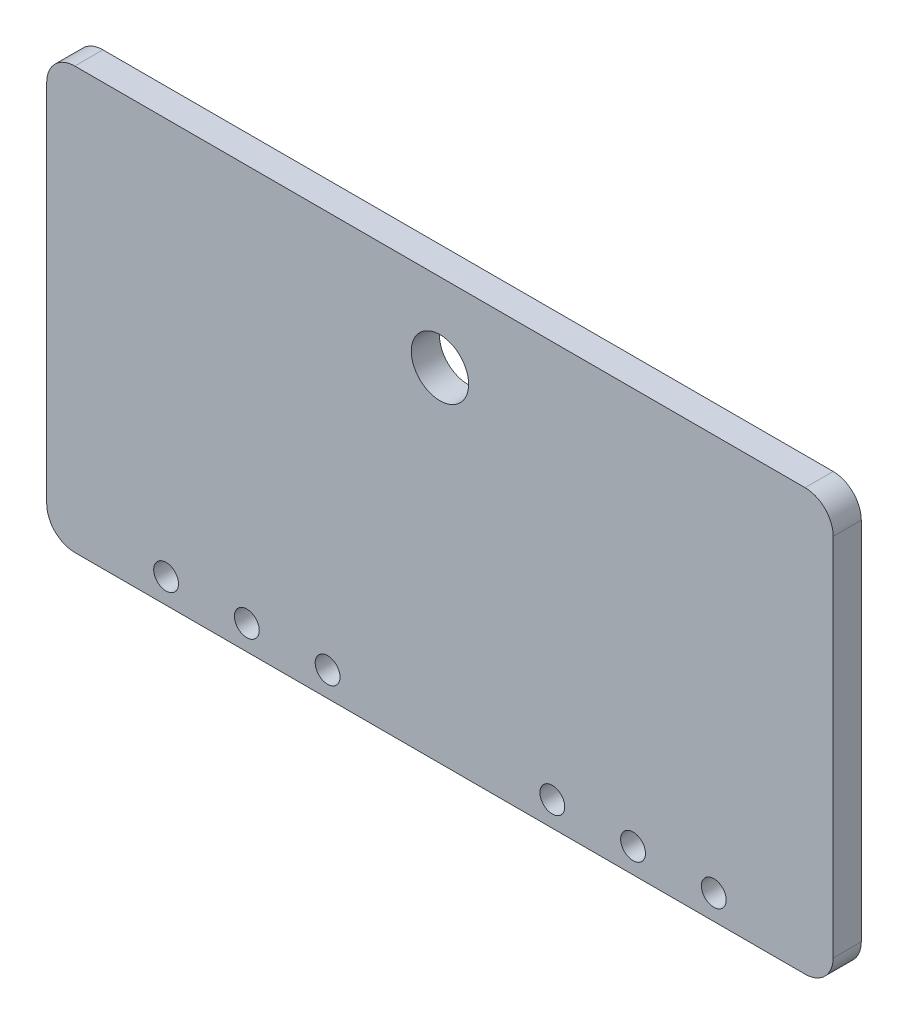
SolidWorks part; units mm, degrees
material "Acrylic (Medium-high impact)"
ref_plane "Front Plane" through (0, 0, 0) normal (0, 0, 1) x (1, 0, 0)
ref_plane "Top Plane" through (0, 0, 0) normal (0, 1, 0) x (1, 0, 0)
ref_plane "Right Plane" through (0, 0, 0) normal (1, 0, 0) x (0, 0, -1)
sketch "Sketch1" plane through (0, 0, 0) normal (0, 0, 1) x (1, 0, 0)
  line L1 (177.8, 95.25) -> (0, 95.25)
  line L2 (177.8, 95.25) -> (177.8, 0)
  line L3 (177.8, 0) -> (0, 0)
  line L4 (0, 95.25) -> (0, 0)
  line L5 (177.8, 95.25) -> (0, 0) construction
  line L6 (177.8, 0) -> (0, 95.25) construction
  point P0 (88.9, 47.625)
  dimension "D1" = 95.25
  dimension "D2" = 177.8
extrude "Boss-Extrude1" add sketch "Sketch1" along normal blind 6.35
hole_wizard "#10 Clearance Hole1" positions "Sketch6" profile "Sketch7" hole size "#10" standard "ANSI Inch" end condition through all
sketch "Sketch6" plane through (0, 0, 6.35) normal (0, 0, 1) x (1, 0, 0)
  line L2 (0, 0) -> (177.8, 0) construction
  line L3 (63.5, 5.588) -> (114.3, 5.588) construction
  line L5 (88.9, 0) -> (88.9, 5.588) construction
  line L6 (26.9875, 5.588) -> (63.5, 5.588) construction
  line L9 (114.3, 5.588) -> (150.8125, 5.588) construction
  point P0 (26.9875, 5.588)
  point P11 (63.5, 5.588)
  point P13 (114.3, 5.588)
  point P15 (150.8125, 5.588)
  point P29 (45.2437, 5.588)
  point P31 (132.5562, 5.588)
  point P45 (45.2437, 5.588)
  point P47 (132.5562, 5.588)
  dimension "D1" = 36.5125
  dimension "D2" = 5.588
  dimension "D5" = 50.8
sketch "Sketch7" plane through (26.9875, 5.588, 6.35) normal (1, 0, 0) x (0, -1, 0)
  line L0 (0, 0) -> (0, 6.35)
  line L1 (0, 6.35) -> (2.8067, 6.35)
  line L2 (2.8067, 6.35) -> (2.8067, 0)
  line L5 (2.8067, 0) -> (0, 0)
  line L11 (0, -6.35) -> (0, 107.95) construction
  dimension "Thru Hole Dia." = 5.6134
  dimension "Thru Hole Depth" = 6.35
sketch "Sketch8" plane through (0, 0, 6.35) normal (0, 0, 1) x (1, 0, 0)
  line L0 (0, 0) -> (177.8, 0) construction
  line L1 (177.8, 95.25) -> (0, 95.25) construction
  circle A0 centre (88.9, 77.47) radius 6.477
  point P6 (88.9, 0)
  dimension "D1" = 12.954
  dimension "D2" = 17.78
extrude "Cut-Extrude1" cut sketch "Sketch8" against normal through all
fillet "Fillet1" radius 6.35 4 edges at (177.8, 0, 3.175) (177.8, 95.25, 3.175) (0, 95.25, 3.175) (0, 0, 3.175)
